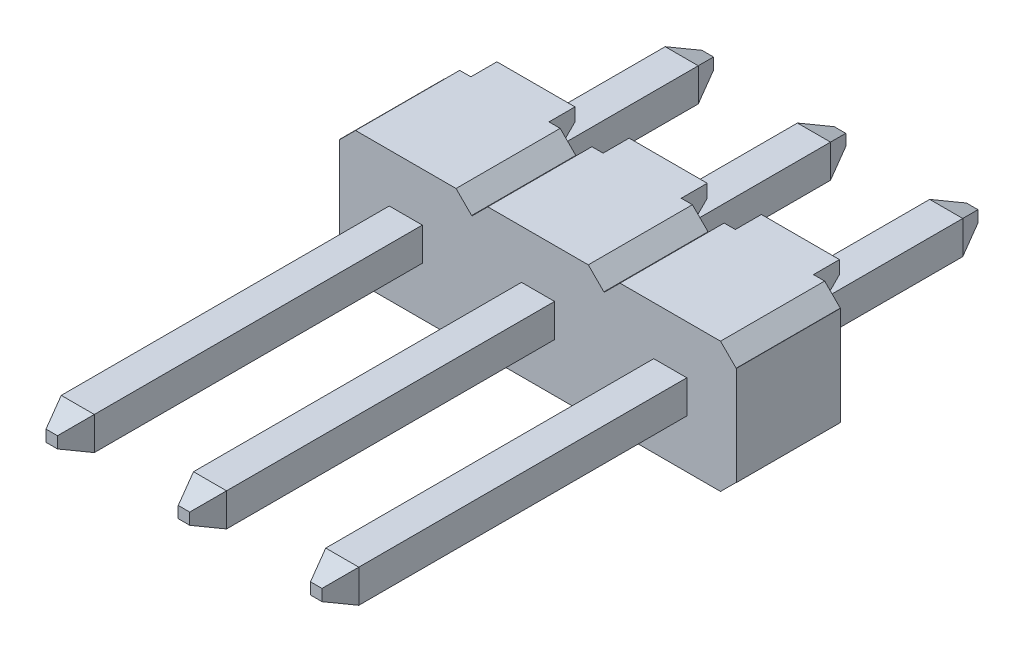
SolidWorks part; units mm, degrees
ref_plane "Front Plane" through (0, 0, 0) normal (0, 0, 1) x (1, 0, 0)
ref_plane "Top Plane" through (0, 0, 0) normal (0, 1, 0) x (1, 0, 0)
ref_plane "Right Plane" through (0, 0, 0) normal (1, 0, 0) x (0, 0, -1)
ref_plane "Plane1" through (0, 0, 0) normal (0, 0, -1) x (-1, 0, 0)
sketch "Sketch1" plane through (0, 0, 0) normal (0, 0, -1) x (-1, 0, 0)
  line L0 (0, 2.5) -> (-7.62, 2.5)
  line L1 (-7.62, 2.5) -> (-7.62, 0)
  line L2 (-7.62, 0) -> (0, 0)
  line L3 (0, 0) -> (0, 2.5)
extrude "Boss-Extrude1" add sketch "Sketch1" against normal blind 2
sketch "Sketch2" plane through (0, 0, 2) normal (0, 0, 1) x (1, 0, 0)
  line L0 (4.775, 2.5) -> (5.385, 1.89)
  line L1 (5.385, 1.89) -> (5.385, 2.5)
  line L2 (5.385, 2.5) -> (4.775, 2.5)
extrude "Cut-Extrude1" cut sketch "Sketch2" against normal through all
sketch "Sketch3" plane through (0, 0, 2) normal (0, 0, 1) x (1, 0, 0)
  line L0 (7.315, 2.5) -> (7.315, 2.2)
  line L1 (7.315, 2.2) -> (7.62, 2.2)
  line L2 (7.62, 2.2) -> (7.62, 2.5)
  line L3 (7.62, 2.5) -> (7.315, 2.5)
extrude "Cut-Extrude2" cut sketch "Sketch3" against normal blind 2
sketch "Sketch4" plane through (0, 0, 2) normal (0, 0, 1) x (1, 0, 0)
  line L0 (7.315, 0.3) -> (7.315, 0)
  line L1 (7.315, 0) -> (7.62, 0)
  line L2 (7.62, 0) -> (7.62, 0.3)
  line L3 (7.62, 0.3) -> (7.315, 0.3)
extrude "Cut-Extrude3" cut sketch "Sketch4" against normal through all
sketch "Sketch5" plane through (0, 0, 2) normal (0, 0, 1) x (1, 0, 0)
  line L0 (5.385, 0) -> (5.385, 0.61)
  line L1 (5.385, 0.61) -> (4.775, 0)
  line L2 (4.775, 0) -> (5.385, 0)
extrude "Cut-Extrude4" cut sketch "Sketch5" against normal through all
sketch "Sketch6" plane through (0, 0, 2) normal (0, 0, 1) x (1, 0, 0)
  line L0 (2.845, 0) -> (2.235, 0.61)
  line L1 (2.235, 0.61) -> (2.235, 0)
  line L2 (2.235, 0) -> (2.845, 0)
extrude "Cut-Extrude5" cut sketch "Sketch6" against normal through all
sketch "Sketch7" plane through (0, 0, 2) normal (0, 0, 1) x (1, 0, 0)
  line L0 (0.305, 0) -> (0.305, 0.3)
  line L1 (0.305, 0.3) -> (0, 0.3)
  line L2 (0, 0.3) -> (0, 0)
  line L3 (0, 0) -> (0.305, 0)
extrude "Cut-Extrude6" cut sketch "Sketch7" against normal blind 2
sketch "Sketch8" plane through (0, 0, 2) normal (0, 0, 1) x (1, 0, 0)
  line L0 (0, 2.5) -> (0, 2.2)
  line L1 (0, 2.2) -> (0.305, 2.2)
  line L2 (0.305, 2.2) -> (0.305, 2.5)
  line L3 (0.305, 2.5) -> (0, 2.5)
extrude "Cut-Extrude7" cut sketch "Sketch8" against normal through all
sketch "Sketch9" plane through (0, 0, 2) normal (0, 0, 1) x (1, 0, 0)
  line L0 (2.235, 2.5) -> (2.235, 1.89)
  line L1 (2.235, 1.89) -> (2.845, 2.5)
  line L2 (2.845, 2.5) -> (2.235, 2.5)
extrude "Cut-Extrude8" cut sketch "Sketch9" against normal through all
sketch "Sketch10" plane through (0, 0, 0) normal (0, 0, -1) x (-1, 0, 0)
  line L0 (-6.6675, 1.5675) -> (-6.0325, 1.5675)
  line L1 (-6.0325, 1.5675) -> (-6.0325, 0.9325)
  line L2 (-6.0325, 0.9325) -> (-6.6675, 0.9325)
  line L3 (-6.6675, 0.9325) -> (-6.6675, 1.5675)
extrude "Boss-Extrude2" add sketch "Sketch10" along normal blind 3.8
sketch "Sketch11" plane through (0, 0, 0) normal (0, 0, -1) x (-1, 0, 0)
  line L0 (-4.1275, 0.9325) -> (-4.1275, 1.5675)
  line L1 (-4.1275, 1.5675) -> (-3.4925, 1.5675)
  line L2 (-3.4925, 1.5675) -> (-3.4925, 0.9325)
  line L3 (-3.4925, 0.9325) -> (-4.1275, 0.9325)
extrude "Boss-Extrude3" add sketch "Sketch11" along normal blind 3.8
sketch "Sketch12" plane through (0, 0, 0) normal (0, 0, -1) x (-1, 0, 0)
  line L0 (-5.6, 0) -> (-7.1, 0)
  line L1 (-7.1, 0) -> (-7.1, 0.75)
  line L2 (-7.1, 0.75) -> (-5.6, 0.75)
  spline S0 degree 1 poles (-5.6, 0) (-5.6, 0.25) (-5.6, 0.75) knots 0 0 1 3 3
extrude "Boss-Extrude4" add sketch "Sketch12" along normal blind 0.5
sketch "Sketch13" plane through (0, 0, 0) normal (0, 0, -1) x (-1, 0, 0)
  line L0 (-3.06, 0) -> (-4.56, 0)
  line L1 (-4.56, 0) -> (-4.56, 0.75)
  line L2 (-4.56, 0.75) -> (-3.06, 0.75)
  spline S0 degree 1 poles (-3.06, 0) (-3.06, 0.25) (-3.06, 0.75) knots 0 0 1 3 3
extrude "Boss-Extrude5" add sketch "Sketch13" along normal blind 0.5
sketch "Sketch14" plane through (0, 0, 0) normal (0, 0, -1) x (-1, 0, 0)
  line L0 (-0.52, 0) -> (-2.02, 0)
  line L1 (-2.02, 0) -> (-2.02, 0.75)
  line L2 (-2.02, 0.75) -> (-0.52, 0.75)
  spline S0 degree 1 poles (-0.52, 0) (-0.52, 0.25) (-0.52, 0.75) knots 0 0 1 3 3
extrude "Boss-Extrude6" add sketch "Sketch14" along normal blind 0.5
sketch "Sketch15" plane through (0, 0, 0) normal (0, 0, -1) x (-1, 0, 0)
  line L0 (-5.6, 1.75) -> (-7.1, 1.75)
  line L1 (-7.1, 2.5) -> (-5.6, 2.5)
  line L2 (-5.6, 2.5) -> (-5.6, 1.75)
  spline S0 degree 1 poles (-7.1, 2.5) (-7.1, 2.25) (-7.1, 1.75) knots -2.2 -2.2 -1.2 0.8 0.8
extrude "Boss-Extrude7" add sketch "Sketch15" along normal blind 0.5
sketch "Sketch16" plane through (0, 0, 0) normal (0, 0, -1) x (-1, 0, 0)
  line L0 (-3.06, 1.75) -> (-4.56, 1.75)
  line L1 (-4.56, 2.5) -> (-3.06, 2.5)
  line L2 (-3.06, 2.5) -> (-3.06, 1.75)
  spline S0 degree 1 poles (-4.56, 2.5) (-4.56, 2.25) (-4.56, 1.75) knots -2.2 -2.2 -1.2 0.8 0.8
extrude "Boss-Extrude8" add sketch "Sketch16" along normal blind 0.5
sketch "Sketch17" plane through (0, 0, 0) normal (0, 0, -1) x (-1, 0, 0)
  line L0 (-0.52, 1.75) -> (-2.02, 1.75)
  line L1 (-2.02, 2.5) -> (-0.52, 2.5)
  line L2 (-0.52, 2.5) -> (-0.52, 1.75)
  spline S0 degree 1 poles (-2.02, 2.5) (-2.02, 2.25) (-2.02, 1.75) knots -2.2 -2.2 -1.2 0.8 0.8
extrude "Boss-Extrude9" add sketch "Sketch17" along normal blind 0.5
sketch "Sketch18" plane through (0, 0, 0) normal (0, 0, -1) x (-1, 0, 0)
  line L0 (-1.5875, 0.9325) -> (-1.5875, 1.5675)
  line L1 (-1.5875, 1.5675) -> (-0.9525, 1.5675)
  line L2 (-0.9525, 1.5675) -> (-0.9525, 0.9325)
  line L3 (-0.9525, 0.9325) -> (-1.5875, 0.9325)
extrude "Boss-Extrude10" add sketch "Sketch18" along normal blind 3.8
sketch "Sketch19" plane through (0, 0, 2) normal (0, 0, 1) x (1, 0, 0)
  line L0 (6.0325, 1.5675) -> (6.6675, 1.5675)
  line L1 (6.6675, 1.5675) -> (6.6675, 0.9325)
  line L2 (6.6675, 0.9325) -> (6.0325, 0.9325)
  line L3 (6.0325, 0.9325) -> (6.0325, 1.5675)
extrude "Boss-Extrude11" add sketch "Sketch19" along normal blind 6.8
sketch "Sketch20" plane through (0, 0, 2) normal (0, 0, 1) x (1, 0, 0)
  line L0 (3.4925, 1.5675) -> (4.1275, 1.5675)
  line L1 (4.1275, 1.5675) -> (4.1275, 0.9325)
  line L2 (4.1275, 0.9325) -> (3.4925, 0.9325)
  line L3 (3.4925, 0.9325) -> (3.4925, 1.5675)
extrude "Boss-Extrude12" add sketch "Sketch20" along normal blind 6.8
sketch "Sketch21" plane through (0, 0, 2) normal (0, 0, 1) x (1, 0, 0)
  line L0 (0.9525, 1.5675) -> (1.5875, 1.5675)
  line L1 (1.5875, 1.5675) -> (1.5875, 0.9325)
  line L2 (1.5875, 0.9325) -> (0.9525, 0.9325)
  line L3 (0.9525, 0.9325) -> (0.9525, 1.5675)
extrude "Boss-Extrude13" add sketch "Sketch21" along normal blind 6.8
draft "Draft1" type of draft neutral plane draft angle 45 faces to draft 2 face at (2.235, 2.195, 1) face at (0.305, 2.35, 1) neutral plane through (0, 2.5, 2) neutral plane normal (0, 1, 0) parameters "D1"=45
draft "Draft2" type of draft neutral plane draft angle 45 faces to draft 2 face at (7.315, 2.35, 1) face at (5.385, 2.195, 1) neutral plane through (0, 2.5, 2) neutral plane normal (0, 1, 0) parameters "D1"=45
draft "Draft3" type of draft neutral plane draft angle 45 faces to draft 2 face at (5.385, 0.305, 1) face at (7.315, 0.15, 1) neutral plane through (7.62, 0, 2) neutral plane normal (0, -1, 0) parameters "D1"=45
draft "Draft4" type of draft neutral plane draft angle 45 faces to draft 2 face at (0.305, 0.15, 1) face at (2.235, 0.305, 1) neutral plane through (7.62, 0, 2) neutral plane normal (0, -1, 0) parameters "D1"=45
draft "Draft5" type of draft neutral plane draft angle 45 faces to draft 6 face at (1.27, 0.75, -0.25) face at (3.81, 0.75, -0.25) face at (6.35, 0.75, -0.25) face at (6.35, 1.75, -0.25) face at (3.81, 1.75, -0.25) face at (1.27, 1.75, -0.25) neutral plane through (0, 0, 0) neutral plane normal (0, 0, -1) parameters "D1"=45
chamfer "Chamfer1" distance 0.0071 angle 45 4 edges at (2.54, 0.305, 1) (2.54, 2.195, 1) (5.08, 2.195, 1) (5.08, 0.305, 1)
chamfer "Chamfer2" distance 0.2071 angle 67.5 24 edges at (1.5875, 1.25, 8.8) (1.27, 0.9325, 8.8) (1.27, 1.5675, 8.8) (0.9525, 1.25, 8.8) (6.6675, 1.25, 8.8) (6.35, 0.9325, 8.8) (6.35, 1.5675, 8.8) (6.0325, 1.25, 8.8) (3.81, 1.5675, -3.8) (4.1275, 1.25, -3.8) (3.4925, 1.25, -3.8) (3.81, 0.9325, -3.8) (1.27, 1.5675, -3.8) (1.5875, 1.25, -3.8) (0.9525, 1.25, -3.8) (1.27, 0.9325, -3.8) (6.0325, 1.25, -3.8) (6.35, 1.5675, -3.8) (6.35, 0.9325, -3.8) (6.6675, 1.25, -3.8) (4.1275, 1.25, 8.8) (3.81, 0.9325, 8.8) (3.81, 1.5675, 8.8) (3.4925, 1.25, 8.8) first distance on face at (1.27, 1.25, 8.8) first distance on face at (6.35, 1.25, 8.8) first distance on face at (3.81, 1.25, -3.8) first distance on face at (1.27, 1.25, -3.8) first distance on face at (6.35, 1.25, -3.8) first distance on face at (3.81, 1.25, 8.8)
ref_plane "Plane2" through (0, 1.25, 0) normal (0, 1, 0) x (1, 0, 0)
ref_plane "Plane3" through (6.35, 0, 0) normal (1, 0, 0) x (0, 0, -1)
ref_axis "Axis1" through (6.35, 1.25, -7.039) along (0, 0, 1)
